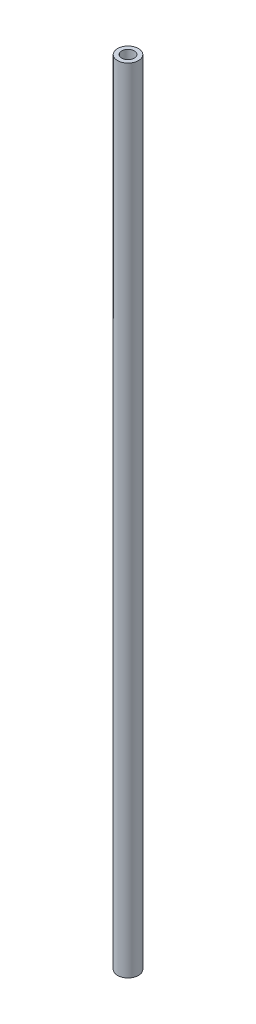
SolidWorks part; units mm, degrees
ref_plane "Front Plane" through (0, 0, 0) normal (0, 0, 1) x (1, 0, 0)
ref_plane "Top Plane" through (0, 0, 0) normal (0, 1, 0) x (1, 0, 0)
ref_plane "Right Plane" through (0, 0, 0) normal (1, 0, 0) x (0, 0, -1)
sketch "Sketch1" plane through (0, 0, 0) normal (0, 1, 0) x (1, 0, 0)
  circle A0 centre (0, 0) radius 4.0259
  circle A1 centre (0, 0) radius 2.4384
  dimension "D2" = 8.0518
  dimension "D1" = 1.5875
extrude "Boss-Extrude1" add sketch "Sketch1" along normal blind 304.8
equation "\"Socket Depth\" = 1.5in'Depth of Sockets in part"
equation "\"Roof Angle\" = 15deg'Angle of spoke to roof"
equation "\"Spoke Diameter\"= .317in'Diameter of spoke"
equation "\"Part Thickness\"= .125in'Thickness of injection-molded walls"
equation "\"Spoke Length\" = 8in'Length of spokes"
equation "\"D2@Sketch1\"= \"Spoke Diameter\""
equation "\"D1@Boss-Extrude1\" = \"Spoke Length2\""
equation "\"Spoke Length2\" = 12in'length of spokes"
equation "\"Center Spoke\" = 16in' lenth of center spoke"
